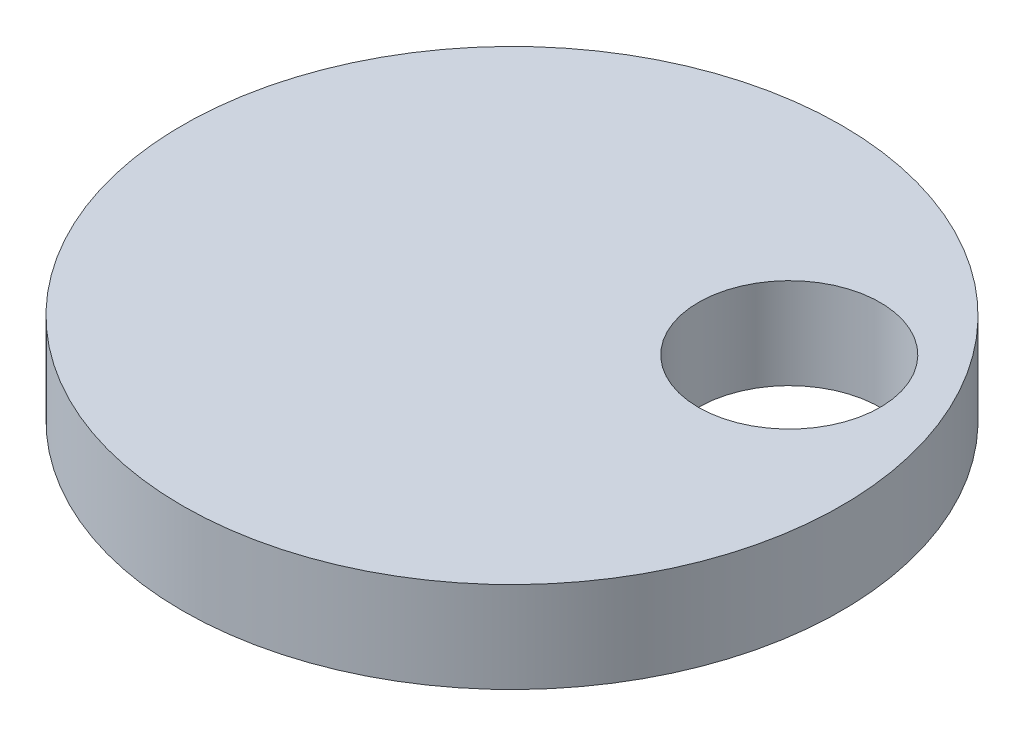
SolidWorks part; units mm, degrees
material "Polyurethane Foam Flexible"
ref_plane "Front Plane" through (0, 0, 0) normal (0, 0, 1) x (1, 0, 0)
ref_plane "Top Plane" through (0, 0, 0) normal (0, 1, 0) x (1, 0, 0)
ref_plane "Right Plane" through (0, 0, 0) normal (1, 0, 0) x (0, 0, -1)
sketch "Sketch1" plane through (0, 0, 0) normal (0, 1, 0) x (1, 0, 0)
  circle A0 centre (0, 0) radius 92.075
  dimension "D1" = 184.15
extrude "Boss-Extrude1" add sketch "Sketch1" along normal blind 25.4
sketch "Sketch2" plane through (0, 25.4, 0) normal (0, 1, 0) x (1, 0, 0)
  circle A0 centre (48.26, 29.21) radius 25.4
  dimension "D1" = 50.8
  dimension "D2" = 29.21
  dimension "D3" = 48.26
extrude "Cut-Extrude1" cut sketch "Sketch2" against normal up to surface (25.4 mm away) up to face at (0, 0, 92.075)
